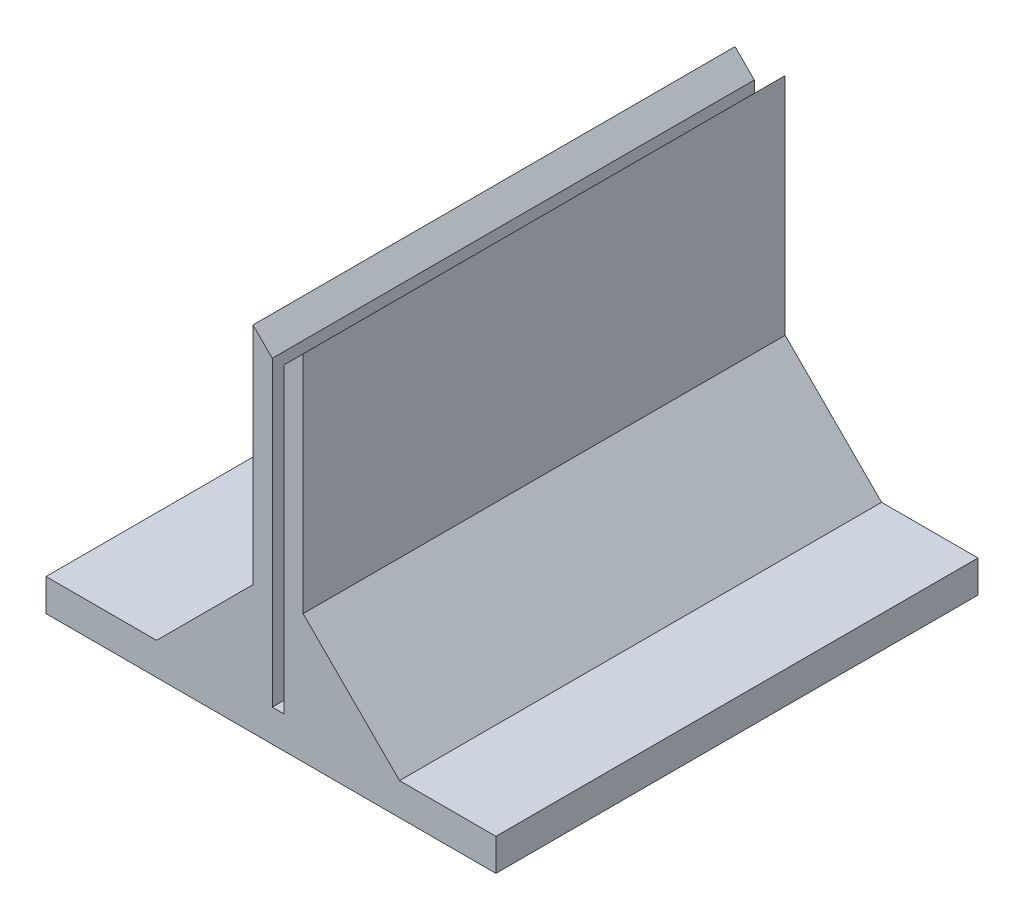
SolidWorks part; units mm, degrees
ref_plane "前视基准面" through (0, 0, 0) normal (0, 0, 1) x (1, 0, 0)
ref_plane "上视基准面" through (0, 0, 0) normal (0, 1, 0) x (1, 0, 0)
ref_plane "右视基准面" through (0, 0, 0) normal (1, 0, 0) x (0, 0, -1)
sketch "草图1" plane through (0, 0, 0) normal (0, 0, 1) x (1, 0, 0)
  line L1 (0, 0) -> (70, 0)
  line L2 (0, 0) -> (0, 5)
  line L3 (0, 5) -> (32.2, 5)
  line L4 (70, 0) -> (70, 5)
  line L5 (35.2, 55) -> (35.2, 5)
  line L6 (40, 5) -> (70, 5)
  line L8 (37, 5) -> (37, 55)
  line L9 (37, 55) -> (40, 55)
  line L10 (40, 5) -> (40, 55)
  line L11 (35.2, 5) -> (37, 5)
  line L12 (32.2, 55) -> (32.2, 5)
  line L13 (35.2, 55) -> (32.2, 55)
  dimension "D1" = 1.8
  dimension "D2" = 3
  dimension "D3" = 30
  dimension "D4" = 70
  dimension "D5" = 50
  dimension "D6" = 5
extrude "凸台-拉伸1" add sketch "草图1" along normal blind 75
chamfer "倒角1" distance 15 angle 45 2 edges at (40, 5, 37.5) (32.2, 5, 37.5)
chamfer "倒角2" distance 3 angle 45 2 edges at (37, 55, 37.5) (35.2, 55, 37.5)
